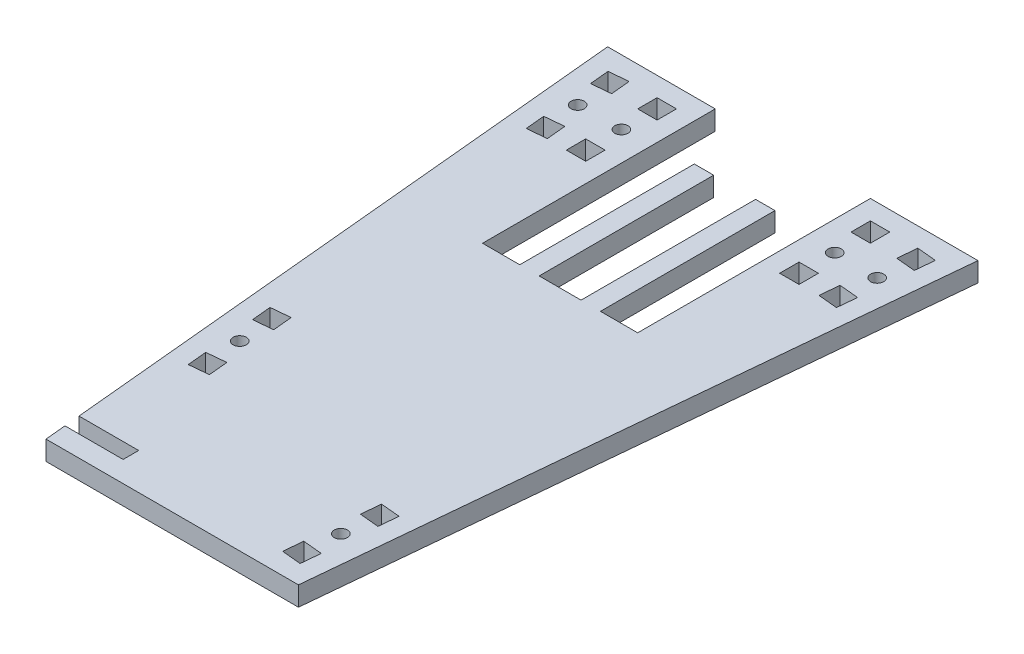
SolidWorks part; units mm, degrees
ref_plane "Front Plane" through (0, 0, 0) normal (0, 0, 1) x (1, 0, 0)
ref_plane "Top Plane" through (0, 0, 0) normal (0, 1, 0) x (1, 0, 0)
ref_plane "Right Plane" through (0, 0, 0) normal (1, 0, 0) x (0, 0, -1)
sketch "Sketch1" plane through (0, 0, 0) normal (0, 1, 0) x (1, 0, 0)
  line L0 (0, 0) -> (0, -183.008) construction
  line L1 (-47.8759, 76.2) -> (-25.4, 76.2)
  line L2 (47.8759, 76.2) -> (28.575, -127) construction
  line L3 (-47.8759, 76.2) -> (-28.575, -127) construction
  line L4 (38.1, 40.132) -> (44.45, 40.132) construction
  line L5 (-47.8759, 76.2) -> (-60.6331, 76.2)
  line L6 (-41.9836, -120.142) -> (-11.3629, -120.142) construction
  line L7 (-57.15, 0) -> (57.15, 0) construction
  line L8 (31.75, 76.2) -> (31.75, 40.132) construction
  line L9 (-31.75, 76.2) -> (-31.75, 40.132) construction
  line L10 (6.858, 57.15) -> (6.858, 0) construction
  line L11 (-6.858, 57.15) -> (-6.858, 0) construction
  line L12 (-6.858, 57.15) -> (-6.858, 0)
  line L13 (-6.858, 0) -> (6.858, 0)
  line L14 (6.858, 0) -> (6.858, 57.15)
  line L15 (6.858, 57.15) -> (13.208, 57.15)
  line L16 (-41.9836, -120.142) -> (-22.9336, -120.142)
  line L17 (-22.9336, -120.142) -> (-22.9336, -115.062)
  line L18 (13.208, 57.15) -> (13.208, 0)
  line L19 (13.208, 0) -> (25.4, 0)
  line L20 (25.4, 0) -> (25.4, 76.2)
  line L21 (25.4, 76.2) -> (47.8759, 76.2)
  line L22 (-25.4, 0) -> (-25.4, 76.2)
  line L23 (-13.208, 0) -> (-25.4, 0)
  line L24 (-13.208, 57.15) -> (-13.208, 0)
  line L25 (-6.858, 0) -> (-6.858, 57.15)
  line L26 (-13.208, 57.15) -> (-6.858, 57.15)
  line L27 (-22.9336, -115.062) -> (-42.4661, -115.062)
  line L28 (-41.9836, -120.142) -> (-41.3322, -127)
  line L29 (47.8759, 76.2) -> (60.6331, 76.2)
  line L30 (60.6331, 76.2) -> (41.3322, -127)
  line L31 (-28.575, -127) -> (0, -127)
  line L32 (0, -127) -> (28.575, -127)
  line L33 (28.575, -127) -> (41.3322, -127)
  line L34 (-60.6331, 76.2) -> (-42.4661, -115.062)
  line L35 (-28.575, -127) -> (-41.3322, -127)
  line L36 (-38.5725, -88.9) -> (-32.251, -88.2995) construction
  line L37 (34.9536, -127) -> (28.632, -126.3995) construction
  line L38 (35.554, -120.6785) -> (34.9536, -127) construction
  line L39 (-39.173, -82.5785) -> (-38.5725, -88.9) construction
  point P0 (0, 0)
  line B0 (34.925, 40.132) -> (34.925, 69.85) construction
  line B1 (32.766, 54.991) -> (37.084, 54.991) construction
  line B2 (31.75, 63.5) -> (38.1, 63.5)
  line B3 (31.75, 63.5) -> (31.75, 69.85)
  line B4 (31.75, 69.85) -> (38.1, 69.85)
  line B5 (38.1, 63.5) -> (38.1, 69.85)
  line B6 (31.75, 63.5) -> (38.1, 69.85) construction
  line B7 (31.75, 69.85) -> (38.1, 63.5) construction
  line B8 (31.75, 40.132) -> (38.1, 46.482) construction
  line B9 (31.75, 46.482) -> (38.1, 40.132) construction
  line B10 (38.1, 46.482) -> (38.1, 40.132)
  line B11 (31.75, 40.132) -> (38.1, 40.132)
  line B12 (31.75, 46.482) -> (31.75, 40.132)
  line B13 (31.75, 46.482) -> (38.1, 46.482)
  circle B14 centre (34.925, 54.991) radius 2.159
  line B15 (-34.925, 40.132) -> (-34.925, 69.85) construction
  line B16 (-32.766, 54.991) -> (-37.084, 54.991) construction
  line B17 (-31.75, 63.5) -> (-38.1, 63.5)
  line B18 (-31.75, 63.5) -> (-31.75, 69.85)
  line B19 (-31.75, 69.85) -> (-38.1, 69.85)
  line B20 (-38.1, 63.5) -> (-38.1, 69.85)
  line B21 (-31.75, 63.5) -> (-38.1, 69.85) construction
  line B22 (-31.75, 69.85) -> (-38.1, 63.5) construction
  line B23 (-31.75, 40.132) -> (-38.1, 46.482) construction
  line B24 (-31.75, 46.482) -> (-38.1, 40.132) construction
  line B25 (-38.1, 46.482) -> (-38.1, 40.132)
  line B26 (-31.75, 40.132) -> (-38.1, 40.132)
  line B27 (-31.75, 46.482) -> (-31.75, 40.132)
  line B28 (-31.75, 46.482) -> (-38.1, 46.482)
  circle B29 centre (-34.925, 54.991) radius 2.159
  line B30 (47.6261, 39.9934) -> (50.4362, 69.5782) construction
  line B31 (46.8819, 54.99) -> (51.1805, 54.5817) construction
  line B32 (46.675, 63.5569) -> (52.9966, 62.9565)
  line B33 (46.675, 63.5569) -> (47.2755, 69.8785)
  line B34 (47.2755, 69.8785) -> (53.597, 69.278)
  line B35 (52.9966, 62.9565) -> (53.597, 69.278)
  line B36 (46.675, 63.5569) -> (53.597, 69.278) construction
  line B37 (47.2755, 69.8785) -> (52.9966, 62.9565) construction
  line B38 (44.4654, 40.2936) -> (51.3873, 46.0147) construction
  line B39 (45.0658, 46.6152) -> (50.7869, 39.6932) construction
  line B40 (51.3873, 46.0147) -> (50.7869, 39.6932)
  line B41 (44.4654, 40.2936) -> (50.7869, 39.6932)
  line B42 (45.0658, 46.6152) -> (44.4654, 40.2936)
  line B43 (45.0658, 46.6152) -> (51.3873, 46.0147)
  circle B44 centre (49.0312, 54.7858) radius 2.159
  line B45 (32.3933, -120.3782) -> (35.2034, -90.7934) construction
  line B46 (31.649, -105.3817) -> (35.9476, -105.79) construction
  line B47 (31.4421, -96.8147) -> (37.7637, -97.4152)
  line B48 (31.4421, -96.8147) -> (32.0426, -90.4932)
  line B49 (32.0426, -90.4932) -> (38.3641, -91.0936)
  line B50 (37.7637, -97.4152) -> (38.3641, -91.0936)
  line B51 (31.4421, -96.8147) -> (38.3641, -91.0936) construction
  line B52 (32.0426, -90.4932) -> (37.7637, -97.4152) construction
  line B53 (29.2325, -120.078) -> (36.1545, -114.3569) construction
  line B54 (29.8329, -113.7565) -> (35.554, -120.6785) construction
  line B55 (36.1545, -114.3569) -> (35.554, -120.6785)
  line B56 (29.2325, -120.078) -> (35.554, -120.6785)
  line B57 (29.8329, -113.7565) -> (29.2325, -120.078)
  line B58 (29.8329, -113.7565) -> (36.1545, -114.3569)
  circle B59 centre (33.7983, -105.5858) radius 2.159
  line B60 (-36.0122, -82.2782) -> (-38.8223, -52.6934) construction
  line B61 (-35.2679, -67.2817) -> (-39.5666, -67.69) construction
  line B62 (-35.0611, -58.7147) -> (-41.3826, -59.3152)
  line B63 (-35.0611, -58.7147) -> (-35.6615, -52.3932)
  line B64 (-35.6615, -52.3932) -> (-41.9831, -52.9936)
  line B65 (-41.3826, -59.3152) -> (-41.9831, -52.9936)
  line B66 (-35.0611, -58.7147) -> (-41.9831, -52.9936) construction
  line B67 (-35.6615, -52.3932) -> (-41.3826, -59.3152) construction
  line B68 (-32.8514, -81.978) -> (-39.7734, -76.2569) construction
  line B69 (-33.4519, -75.6565) -> (-39.173, -82.5785) construction
  line B70 (-39.7734, -76.2569) -> (-39.173, -82.5785)
  line B71 (-32.8514, -81.978) -> (-39.173, -82.5785)
  line B72 (-33.4519, -75.6565) -> (-32.8514, -81.978)
  line B73 (-33.4519, -75.6565) -> (-39.7734, -76.2569)
  circle B74 centre (-37.4172, -67.4858) radius 2.159
  line B75 (-47.6261, 39.9934) -> (-50.4362, 69.5782) construction
  line B76 (-46.8819, 54.99) -> (-51.1805, 54.5817) construction
  line B77 (-46.675, 63.5569) -> (-52.9966, 62.9565)
  line B78 (-46.675, 63.5569) -> (-47.2755, 69.8785)
  line B79 (-47.2755, 69.8785) -> (-53.597, 69.278)
  line B80 (-52.9966, 62.9565) -> (-53.597, 69.278)
  line B81 (-46.675, 63.5569) -> (-53.597, 69.278) construction
  line B82 (-47.2755, 69.8785) -> (-52.9966, 62.9565) construction
  line B83 (-44.4654, 40.2936) -> (-51.3873, 46.0147) construction
  line B84 (-45.0658, 46.6152) -> (-50.7869, 39.6932) construction
  line B85 (-51.3873, 46.0147) -> (-50.7869, 39.6932)
  line B86 (-44.4654, 40.2936) -> (-50.7869, 39.6932)
  line B87 (-45.0658, 46.6152) -> (-44.4654, 40.2936)
  line B88 (-45.0658, 46.6152) -> (-51.3873, 46.0147)
  circle B89 centre (-49.0312, 54.7858) radius 2.159
  dimension "D1" = 63.5
  dimension "D2" = 6.35
  dimension "D3" = 6.858
  dimension "D4" = 57.15
  dimension "D5" = 6.858
  dimension "D6" = 5.08
  dimension "D7" = 19.05
  dimension "D8" = 203.2
  dimension "D9" = 6.35
  dimension "D10" = 6.35
  dimension "D11" = 6.35
  dimension "D12" = 76.2
  dimension "D13" = 6.35
  dimension "D14" = 6.35
  dimension "D15" = 38.1
  dimension "D16" = 127
  dimension "D17" = 93.1039
  dimension "D18" = 131.3754
  dimension "D19" = 19.05
sketch_block_instance "Female T-Slot Assembly-1"
sketch_block "Female T-Slot Assembly" parameters "D4"=4.318, "D1"=6.35, "D2"=6.35, "D3"=6.35
sketch_block_instance "Female T-Slot Assembly-3"
sketch_block_instance "Female T-Slot Assembly-1"
sketch_block_instance "Female T-Slot Assembly-14"
sketch_block_instance "Female T-Slot Assembly-16"
sketch_block_instance "Female T-Slot Assembly-17"
extrude "Boss-Extrude1" add sketch "Sketch1" along normal blind 6.35 contours L26 L24 L23 L22 L1 L21 L20 L19 L18 L15 L14 L13 L12 B29 B28 B27 B26 B25 B12 B13 B10 B11 B5 B2 B3 region at (0.2093, 0, 30.3528)
equation "\"Ball Diameter\"= 1.75in"
equation "\"Ball Radius\" = \"Ball Diameter\"/2"
equation "\"Sheet Thickness\"= 0.25in"
equation "\"Screw Diameter\"= .17in"
equation "\"Robot Diameter\"= 14in"
equation "\"Castor Screw Diameter\"= 0.22in"
equation "\"Wheel Diameter\" = 4in"
equation "\"Nut Diameter\" = 8.4mm"
equation "\"Nut Height\" = 2.9mm"
equation "\"Screw Height\" = 0.55in"
equation "\"Pulley Diameter\" = 1in"
equation "\"Reactor Height\" = 14in"
equation "\"Elevator Height\" = 11.5in"
equation "\"Elevator Width\" = \"Ball Diameter\" + 0.25in"
equation "\"Elevator Bearing Diameter\" = sqr(2*(\"Sheet Thickness\"^2)) + 0.2in"
equation "\"Elevator Axle Endcap Diameter\" = \"Pulley Diameter\" + 0.25in"
equation "\"Elevator Axle Length\" = \"Elevator Width\" + 8*\"Sheet Thickness\""
equation "\"Elevator Clearance from Axis\" = 3.28in"
equation "\"Elevator Horizontal Clearance\" = \"Elevator Width\" + 0.5in"
equation "\"Claw Horizontal Seperation\" = (\"Elevator Width\"/2) - (1.5 * \"Sheet Thickness\") - 0.15in"
equation "\"Claw Radius\" = \"Ball Radius\" + 0.1in"
equation "\"Castor Wheel Height\" = 1.25in"
equation "\"Length of Chute\" = 8in"
equation "\"D4@Sketch1\"=\"Ball Diameter\" + 0.5in"
equation "\"D8@Sketch1\"=\"Length of Chute\""
